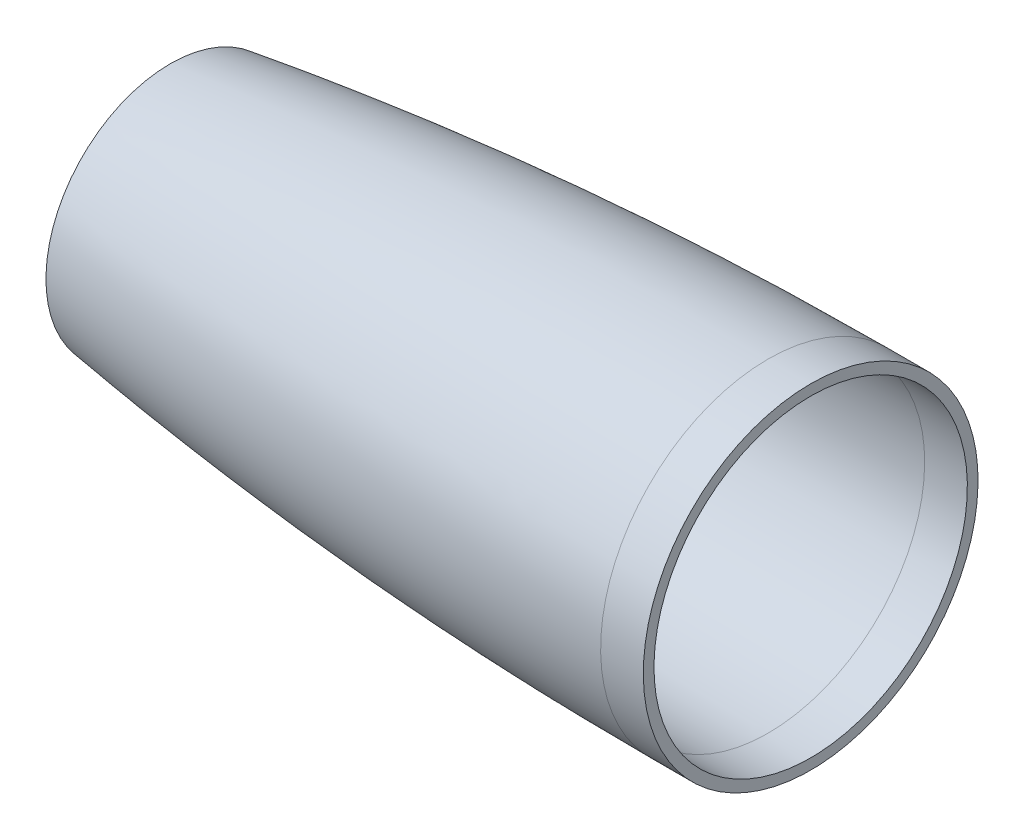
SolidWorks part; units mm, degrees
ref_plane "Front Plane" through (0, 0, 0) normal (0, 0, 1) x (1, 0, 0)
ref_plane "Top Plane" through (0, 0, 0) normal (0, 1, 0) x (1, 0, 0)
ref_plane "Right Plane" through (0, 0, 0) normal (1, 0, 0) x (0, 0, -1)
sketch "Sketch1" plane through (0, 0, 0) normal (0, 0, 1) x (1, 0, 0)
  line L0 (304.8, 49.784) -> (304.8, 0)
  line L1 (304.8, 0) -> (0, 0)
  line L2 (0, 0) -> (0, 11.7484)
  spline S0 degree 4 poles (-29.5658, 3.8633) (-28.9441, 4.0374) (-27.7007, 4.3845) (-25.2159, 5.0746) (-22.1117, 5.9273) (-19.0277, 6.7655) (-15.9353, 7.5966) (-13.5064, 8.2445) (-11.0138, 8.9031) (-8.6496, 9.5239) (-6.017, 10.2074) (-3.9348, 10.7459) (-0.8664, 11.529) (0.5497, 11.8883) (3.0854, 12.5273) (5.1062, 13.0323) (7.1101, 13.5293) (9.1599, 14.0344) (11.1954, 14.5321) (13.2334, 15.0269) (15.805, 15.6465) (18.9103, 16.3873) (22.5507, 17.2447) (26.7272, 18.2131) (31.9522, 19.4057) (42.4129, 21.7425) (62.3339, 25.9764) (110.7705, 35.2251) (160.7073, 42.1599) (207.7023, 46.435) (245.168, 48.3682) (253.7348, 48.741) (260.1614, 48.9835) (264.4463, 49.1304) (268.7317, 49.2625) (273.0175, 49.3798) (277.3037, 49.4823) (281.5902, 49.5699) (285.3296, 49.6334) (288.5217, 49.6785) (291.1667, 49.7098) (293.2638, 49.7311) (295.3592, 49.7488) (297.4702, 49.763) (299.5351, 49.7737) (301.6172, 49.7807) (304.2305, 49.7845) (305.6886, 49.7842) (308.8437, 49.7793) (310.9886, 49.769) (313.6963, 49.7536) (316.1321, 49.733) (318.7003, 49.7073) (321.2035, 49.6765) (323.7502, 49.6404) (326.2925, 49.5988) (328.8544, 49.5518) (331.4237, 49.4993) (333.3523, 49.4559) (334.6374, 49.4252) (335.2799, 49.4094) knots 0 0 0 0 0 0.006994 0.013988 0.027976 0.034844 0.041712 0.048579 0.055447 0.062315 0.069182 0.07605 0.082918 0.088602 0.094285 0.099969 0.105653 0.111336 0.11702 0.122704 0.128387 0.140005 0.151623 0.163241 0.174859 0.198094 0.267801 0.38398 0.709279 0.744133 0.778986 0.790604 0.802222 0.81384 0.825458 0.837075 0.848693 0.860311 0.871929 0.877613 0.883296 0.88898 0.894664 0.900347 0.906031 0.911715 0.917398 0.92424 0.931081 0.937923 0.944764 0.951606 0.958447 0.965289 0.97213 0.979098 0.986065 0.993033 1 1 1 1 1 construction
  spline S1 degree 4 poles (0, 11.7484) (0.4242, 11.8559) (1.2778, 12.0717) (3.0854, 12.5273) (5.1062, 13.0323) (7.1101, 13.5293) (9.1599, 14.0344) (11.1954, 14.5321) (13.2334, 15.0269) (15.805, 15.6465) (18.9103, 16.3873) (22.5507, 17.2447) (26.7272, 18.2131) (31.9522, 19.4057) (42.4129, 21.7425) (62.3339, 25.9764) (110.7705, 35.2251) (160.7073, 42.1599) (207.7023, 46.435) (245.168, 48.3682) (253.7348, 48.741) (260.1614, 48.9835) (264.4463, 49.1304) (268.7317, 49.2625) (273.0175, 49.3798) (277.3037, 49.4823) (281.5902, 49.5699) (285.3296, 49.6334) (288.5217, 49.6785) (291.1667, 49.7098) (293.2638, 49.7311) (295.3592, 49.7488) (297.4702, 49.763) (299.5351, 49.7737) (301.6172, 49.7807) (303.4822, 49.7834) (304.3624, 49.784) (304.8, 49.784) knots 0.082918 0.082918 0.082918 0.082918 0.082918 0.088602 0.094285 0.099969 0.105653 0.111336 0.11702 0.122704 0.128387 0.140005 0.151623 0.163241 0.174859 0.198094 0.267801 0.38398 0.709279 0.744133 0.778986 0.790604 0.802222 0.81384 0.825458 0.837075 0.848693 0.860311 0.871929 0.877613 0.883296 0.88898 0.894664 0.900347 0.906031 0.911715 0.917398 0.917398 0.917398 0.917398 0.917398
  dimension "D1" = 49.784
  dimension "D2" = 304.8
revolve "Revolve1" add sketch "Sketch1" angle 360 about L1
sketch "Sketch2" plane through (304.8, 0, 0) normal (1, 0, 0) x (0, 0, -1)
  circle A0 centre (0, 0) radius 49.784
extrude "Boss-Extrude1" add sketch "Sketch2" along normal blind 203.2
sketch "Sketch3" plane through (0, 0, 0) normal (-1, 0, 0) x (0, 0, 1)
  circle A0 centre (0, 0) radius 11.7484
extrude "Boss-Extrude2" add sketch "Sketch3" along normal blind 50.8
ref_plane "Plane1" through (317.5, 0, 0) normal (1, 0, 0) x (0, 0, -1)
ref_plane "Plane2" through (127, 0, 0) normal (1, 0, 0) x (0, 0, -1)
sketch "Sketch4" plane through (317.5, 0, 0) normal (1, 0, 0) x (0, 0, -1)
  circle A0 centre (0, 0) radius 54.5989
extrude "Cut-Extrude1" cut sketch "Sketch4" along normal through all
sketch "Sketch5" plane through (127, 0, 0) normal (1, 0, 0) x (0, 0, -1)
  circle A0 centre (0, 0) radius 59.5526
extrude "Cut-Extrude2" cut sketch "Sketch5" against normal through all
shell "Shell1" thickness 3.175 removed face at (317.5, 49.784, 0) removed face at (127, 36.9736, 0)
